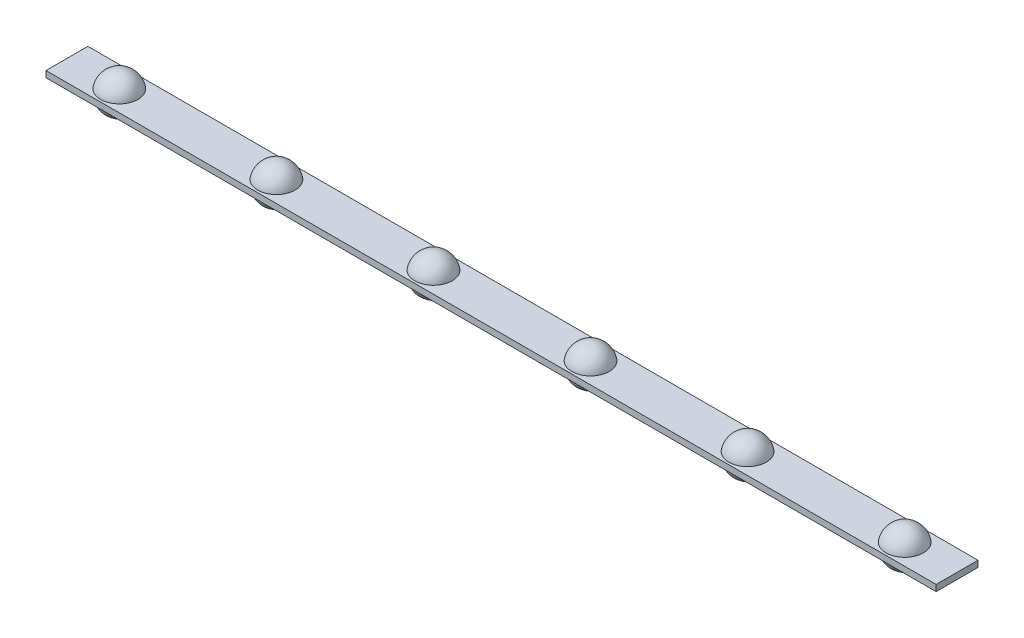
SolidWorks part; units mm, degrees
ref_plane "Front" through (0, 0, 0) normal (0, 0, 1) x (1, 0, 0)
ref_plane "Top" through (0, 0, 0) normal (0, 1, 0) x (1, 0, 0)
ref_plane "Right" through (0, 0, 0) normal (1, 0, 0) x (0, 0, -1)
sketch "Sketch1" plane through (0, 0, 0) normal (1, 0, 0) x (0, 0, -1)
  line L1 (5.6388, 0) -> (-5.6388, 0) construction
  line L4 (-4.1393, 22.8203) -> (-0.7433, 22.6989)
  line L5 (-1.1312, 21.5182) -> (-4.1819, 21.6273)
  line L6 (-4.445, 18.415) -> (-5.6388, 18.415)
  line L7 (-4.445, 21.3734) -> (-4.445, 18.415)
  line L8 (-5.6388, 18.415) -> (-5.6388, 21.3734)
  line L9 (3.9237, 21.6269) -> (0.7619, 21.5441)
  line L10 (5.6388, 0) -> (5.6388, 21.1191)
  line L11 (4.445, 21.1191) -> (4.445, 0)
  line L12 (5.6388, 0) -> (4.445, 0)
  line L13 (-0.7433, 22.6989) -> (3.8925, 22.8203)
  arc A0 (-4.445, 21.3734) -> (-4.1819, 21.6273) centre (-4.191, 21.3734) cw
  arc A1 (-5.6388, 21.3734) -> (-4.1393, 22.8203) centre (-4.191, 21.3734) cw
  arc A3 (3.9237, 21.6269) -> (4.445, 21.1191) centre (3.937, 21.1191) cw
  arc A4 (3.8925, 22.8203) -> (5.6388, 21.1191) centre (3.937, 21.1191) cw
  arc A5 (-1.1312, 21.5182) -> (0.7619, 21.5441) centre (-0.1524, 19.1744) cw
  dimension "D2" = 19.1744
  dimension "D7" = 0.254
  dimension "D8" = 0.508
  dimension "D6" = 2.54
  dimension "D9" = 1.1938
  dimension "D10" = 88.5
  dimension "D1" = 11.2776
  dimension "D3" = 5.7912
  dimension "D4" = 36.83
  dimension "D5" = 1.1938
  dimension "D11" = 87.953
  dimension "D12" = 45.6406
extrude "Extrude1" add sketch "Sketch1" along normal mid plane 400.05
ref_plane "Travel / 2" through (-403.225, 0, 0) normal (-1, 0, 0) x (0, 0, 1)
sketch "Sketch2" plane through (-403.225, 0, 0) normal (-1, 0, 0) x (0, 0, 1)
  line L0 (0.0254, 6.1159) -> (0.0254, 0)
  line L2 (-5.6388, 0) -> (5.6388, 0) construction
  line L3 (5.6388, 21.3734) -> (5.6388, 18.415) construction
  line L7 (-4.445, 21.1191) -> (-4.445, 0) construction
  line L8 (-5.6388, 0) -> (-5.6388, 21.1191) construction
  line L13 (-3.5306, 16.3766) -> (-3.5306, 9.5217)
  line L46 (-2.3867, 7.7262) -> (-0.4146, 6.8065)
  arc A0 (0.0254, 6.1159) -> (-0.4146, 6.8065) centre (-0.7366, 6.1159) ccw
  arc A1 (-1.5056, 17.2916) -> (1.2415, 16.9143) centre (0.1524, 19.1744) ccw
  arc A4 (1.1312, 21.5182) -> (-0.7619, 21.5441) centre (0.1524, 19.1744) ccw construction
  arc A19 (-3.5306, 9.5217) -> (-2.3867, 7.7262) centre (-1.5494, 9.5217) ccw
  arc A25 (-1.5056, 17.2916) -> (-3.5306, 16.3766) centre (-2.3114, 16.3766) ccw
  arc A51 (5.7404, 15.6277) -> (1.2415, 16.9143) centre (2.7686, 13.7451) ccw
  dimension "D2" = 8.4074
  dimension "D3" = 27.4903
  dimension "D6" = 1.9812
  dimension "D8" = 12.2319
  dimension "D10" = 2.5088
  dimension "D11" = 1.2192
  dimension "D4" = 0.762
  dimension "D5" = 4.4704
  dimension "D7" = 115
  dimension "D9" = 19.0435
  dimension "D13" = 11.3792
extrude "Middle Member" add sketch "Sketch2" against normal blind 400.05 separate body thin thin type one direction reverse wall 1.2192
ref_plane "Travel" through (-606.425, 0, 0) normal (-1, 0, 0) x (0, 0, 1)
sketch "Sketch3" plane through (-606.425, 0, 0) normal (-1, 0, 0) x (0, 0, 1)
  line L0 (1.2446, 0) -> (0.0254, 0) construction
  line L1 (-5.6388, 0) -> (-5.6388, 21.1191) construction
  line L56 (7.0612, 0) -> (7.0612, 10.6235)
  line L93 (5.5372, 12.1475) -> (5.1643, 12.1475)
  arc A0 (1.2082, 11.9072) -> (4.2365, 11.8325) centre (2.7686, 13.7451) ccw
  arc A29 (7.0612, 10.6235) -> (5.5372, 12.1475) centre (5.5372, 10.6235) ccw
  arc A53 (5.1643, 12.1475) -> (4.2365, 11.8325) centre (5.1643, 10.6235) ccw
  dimension "D1" = 1.524
  dimension "D4" = 1.524
  dimension "D5" = 2.411
  dimension "D2" = 12.7
  dimension "D3" = 12.1475
  dimension "D6" = 5.853
extrude "Drawer Member" add sketch "Sketch3" against normal blind 400.05 thin thin type one direction wall 1.397
sketch "Sketch6" plane through (0, 0, 7.0612) normal (0, 0, 1) x (1, 0, 0)
  line L1 (-606.425, 0) -> (-604.52, 0)
  line L2 (-606.425, 0) -> (-606.425, 12.1475)
  line L3 (-606.425, 12.1475) -> (-604.52, 12.1475)
  line L4 (-604.52, 0) -> (-604.52, 12.1475)
  line L5 (-206.375, 12.1475) -> (-606.425, 12.1475) construction
  line L7 (-606.425, 10.6235) -> (-606.425, 0) construction
  line L8 (-206.375, 0) -> (-606.425, 0) construction
  dimension "D1" = 1.905
extrude "Cut-Extrude1" cut sketch "Sketch6" against normal through all
sketch "Sketch8" plane through (0, 0, -4.445) normal (0, 0, 1) x (1, 0, 0)
  line L0 (190.3865, 7.6456) -> (191.8208, 7.493)
  line L1 (200.025, 12.2048) -> (190.6284, 12.2048)
  line L2 (191.8208, 7.493) -> (191.8208, 0)
  line L3 (200.025, 0) -> (-200.025, 0) construction
  line L4 (200.025, 21.1191) -> (200.025, 0) construction
  line L5 (200.025, 12.2048) -> (200.025, 0)
  line L6 (200.025, 0) -> (191.8208, 0)
  arc A0 (190.6284, 12.2048) -> (190.3865, 7.6456) centre (190.6284, 9.9188) ccw
  dimension "D3" = 9.9188
  dimension "D1" = 12.2048
  dimension "D2" = 8.2042
  dimension "D4" = 9.3966
  dimension "D5" = 7.493
extrude "Cut-Extrude2" cut sketch "Sketch8" against normal up to next (1.1938 mm away)
sketch "Sketch11" plane through (0, 0, 7.0612) normal (0, 0, 1) x (1, 0, 0)
  line L0 (-212.09, 5.9678) -> (-212.09, 0)
  line L8 (-206.375, 8.5893) -> (-212.2343, 7.2212)
  line L11 (-212.09, 0) -> (-206.375, 0)
  line L12 (-206.375, 0) -> (-206.375, 8.5893)
  arc A1 (-212.2343, 7.2212) -> (-212.09, 5.9678) centre (-212.0899, 6.6028) ccw
  dimension "D3" = 0.635
  dimension "D1" = 5.715
  dimension "D2" = 8.5893
  dimension "D4" = 5.9678
  dimension "D5" = 103.143
extrude "Cut-Extrude3" cut sketch "Sketch11" against normal up to next (1.397 mm away)
sketch "Sketch12" plane through (0, 0, 1.2446) normal (0, 0, 1) x (1, 0, 0)
  line L0 (-3.175, 12.065) -> (-13.335, 12.065)
  line L1 (-3.175, 16.3766) -> (-3.175, 9.5217) construction
  line L2 (-15.875, 9.525) -> (-15.875, 0)
  line L3 (-3.175, 0) -> (-403.225, 0) construction
  line L4 (-15.875, 0) -> (-3.175, 0)
  line L5 (-3.175, 0) -> (-3.175, 12.065)
  arc A0 (-13.335, 12.065) -> (-15.875, 9.525) centre (-13.335, 9.525) ccw
  point P11 (-15.875, 12.065)
  dimension "D3" = 2.54
  dimension "D1" = 12.7
  dimension "D2" = 12.065
extrude "Cut-Extrude4" cut sketch "Sketch12" against normal through all
sketch "Sketch13" plane through (0, 0, -4.445) normal (0, 0, 1) x (1, 0, 0)
  line L0 (-131.6367, 7.112) -> (-156.4652, 7.112)
  line L1 (191.8208, 0) -> (-200.025, 0) construction
  line L2 (-139.7266, 0) -> (-139.7266, 4.2392) construction
  line L3 (-182.5637, 10.287) -> (-131.6367, 10.287)
  line L4 (-200.025, 21.1191) -> (-200.025, 0) construction
  line L5 (-160.2752, 7.112) -> (-182.5637, 7.112)
  line L6 (-159.5132, 0) -> (-159.5132, 6.35)
  line L7 (-157.2272, 6.35) -> (-157.2272, 0)
  line L8 (-137.2501, 2.286) -> (-142.2031, 2.286)
  line L13 (-176.3026, 0) -> (-171.7306, 0)
  line L14 (-168.2, 0) -> (-161.85, 0)
  line L15 (-159.5132, 0) -> (-157.2272, 0)
  line L16 (-154.7126, 0) -> (-150.1406, 0)
  line L17 (-144.4891, 0) -> (-134.9641, 0)
  arc A1 (-182.5637, 10.287) -> (-182.5637, 7.112) centre (-182.5637, 8.6995) ccw
  arc A2 (-159.5132, 6.35) -> (-160.2752, 7.112) centre (-160.2752, 6.35) ccw
  arc A4 (-156.4652, 7.112) -> (-157.2272, 6.35) centre (-156.4652, 6.35) ccw
  arc A7 (-131.6367, 7.112) -> (-131.6367, 10.287) centre (-131.6367, 8.6995) ccw
  arc A8 (-161.85, 0) -> (-168.2, 0) centre (-165.025, 0) ccw
  arc A9 (-171.7306, 0) -> (-176.3026, 0) centre (-174.0166, 0) ccw
  arc A10 (-150.1406, 0) -> (-154.7126, 0) centre (-152.4266, 0) ccw
  arc A11 (-134.9641, 0) -> (-137.2501, 2.286) centre (-137.2501, 0) ccw
  arc A12 (-142.2031, 2.286) -> (-144.4891, 0) centre (-142.2031, 0) ccw
  dimension "D3" = 2.286
  dimension "D4" = 3.175
  dimension "D7" = 8.9916
  dimension "D8" = 21.59
  dimension "D9" = 34.29
  dimension "D10" = 0.762
  dimension "D11" = 17.5387
  dimension "D12" = 9.525
  dimension "D13" = 5.5118
  dimension "D14" = 35
  dimension "D1" = 3.175
  dimension "D2" = 50.927
  dimension "D5" = 2.286
  dimension "D6" = 10.287
extrude "Cut-Extrude5" cut sketch "Sketch13" against normal up to next (1.1938 mm away)
sketch "Sketch32" plane through (0, 0, -5.6388) normal (0, 0, -1) x (-1, 0, 0)
  line L0 (19.5625, 0) -> (29.0875, 0)
  line L1 (33.85, 0) -> (40.2, 0)
  line L2 (43.6925, 0) -> (53.2175, 0)
  line L3 (56.583, 0) -> (61.155, 0)
  line L4 (-191.8208, 0) -> (134.9641, 0) construction
  line L5 (182.5637, 10.287) -> (131.6367, 10.287) construction
  line L6 (131.6367, 7.112) -> (156.4652, 7.112) construction
  line L7 (48.455, 2.286) -> (48.455, -3.4269) construction
  line L8 (24.325, 2.286) -> (24.325, -3.4269) construction
  line L14 (16.3875, 10.287) -> (59.631, 10.287)
  line L15 (55.059, 7.112) -> (16.3875, 7.112)
  line L17 (61.155, 8.763) -> (61.155, 0)
  line L18 (56.583, 0) -> (56.583, 5.588)
  line L23 (21.8485, 2.286) -> (26.8015, 2.286)
  line L25 (45.9785, 2.286) -> (50.9315, 2.286)
  arc A0 (168.2, 0) -> (161.85, 0) centre (165.025, 0) ccw construction
  arc A13 (61.155, 8.763) -> (59.631, 10.287) centre (59.631, 8.763) ccw
  arc A14 (56.583, 5.588) -> (55.059, 7.112) centre (55.059, 5.588) ccw
  arc A17 (16.3875, 10.287) -> (16.3875, 7.112) centre (16.3875, 8.6995) ccw
  arc A20 (29.0875, 0) -> (26.8015, 2.286) centre (26.8015, 0) ccw
  arc A21 (21.8485, 2.286) -> (19.5625, 0) centre (21.8485, 0) ccw
  arc A22 (40.2, 0) -> (33.85, 0) centre (37.025, 0) ccw
  arc A24 (53.2175, 0) -> (50.9315, 2.286) centre (50.9315, 0) ccw
  arc A25 (45.9785, 2.286) -> (43.6925, 0) centre (45.9785, 0) ccw
  dimension "D2" = 1.524
  dimension "D3" = 3.175
  dimension "D4" = 9.525
  dimension "D5" = 2.286
  dimension "D6" = 11.43
  dimension "D7" = 12.7
  dimension "D8" = 24.13
  dimension "D9" = 20.6375
  dimension "D10" = 128
  dimension "D1" = 4.572
extrude "Cut-Extrude14" cut sketch "Sketch32" against normal up to next (1.1938 mm away)
sketch "Sketch33" plane through (83.6094, 0.8125, -5.6388) normal (0, 0, -1) x (-1, 0, 0)
  line L0 (7.1719, -0.8125) -> (16.6969, -0.8125) construction
  line L1 (21.4594, -0.8125) -> (27.8094, -0.8125)
  line L2 (31.3019, -0.8125) -> (40.8269, -0.8125)
  line L3 (44.1924, -0.8125) -> (48.7644, -0.8125)
  line L4 (9.6484, -0.8125) -> (14.2204, -0.8125)
  line L7 (36.0644, 1.4735) -> (36.0644, -4.2394) construction
  line L8 (11.9344, 1.4735) -> (11.9344, -3.4269) construction
  line L9 (-108.2114, -0.8125) -> (103.1719, -0.8125) construction
  line L10 (143.2404, 9.4745) -> (99.9969, 9.4745) construction
  line L11 (99.9969, 6.2995) -> (138.6684, 6.2995) construction
  line L14 (3.9969, 9.4745) -> (47.2404, 9.4745)
  line L15 (42.6684, 6.2995) -> (3.9969, 6.2995)
  line L17 (48.7644, 7.9505) -> (48.7644, -0.8125)
  line L18 (44.1924, -0.8125) -> (44.1924, 4.7755)
  line L23 (9.4579, 1.4735) -> (14.4109, 1.4735) construction
  line L25 (33.5879, 1.4735) -> (38.5409, 1.4735)
  arc A0 (14.2204, -0.8125) -> (9.6484, -0.8125) centre (11.9344, -0.8125) ccw
  arc A1 (251.8094, -0.8125) -> (245.4594, -0.8125) centre (248.6344, -0.8125) ccw construction
  arc A13 (48.7644, 7.9505) -> (47.2404, 9.4745) centre (47.2404, 7.9505) ccw
  arc A14 (44.1924, 4.7755) -> (42.6684, 6.2995) centre (42.6684, 4.7755) ccw
  arc A17 (3.9969, 9.4745) -> (3.9969, 6.2995) centre (3.9969, 7.887) ccw
  arc A20 (16.6969, -0.8125) -> (14.4109, 1.4735) centre (14.4109, -0.8125) ccw construction
  arc A21 (9.4579, 1.4735) -> (7.1719, -0.8125) centre (9.4579, -0.8125) ccw construction
  arc A22 (27.8094, -0.8125) -> (21.4594, -0.8125) centre (24.6344, -0.8125) ccw
  arc A24 (40.8269, -0.8125) -> (38.5409, 1.4735) centre (38.5409, -0.8125) ccw
  arc A25 (33.5879, 1.4735) -> (31.3019, -0.8125) centre (33.5879, -0.8125) ccw
  dimension "D2" = 1.524
  dimension "D3" = 3.175
  dimension "D4" = 9.525
  dimension "D5" = 2.286
  dimension "D6" = 11.43
  dimension "D7" = 12.7
  dimension "D8" = 24.13
  dimension "D9" = 20.6375
  dimension "D10" = 224
  dimension "D1" = 4.572
extrude "Cut F" cut sketch "Sketch33" against normal up to next (1.1938 mm away)
sketch "Sketch34" plane through (169.8236, 1.4527, -5.6388) normal (0, 0, -1) x (-1, 0, 0)
  line L0 (-2.6539, -1.4527) -> (6.8711, -1.4527)
  line L1 (11.6336, -1.4527) -> (17.9836, -1.4527)
  line L2 (21.4761, -1.4527) -> (31.0011, -1.4527)
  line L3 (34.3666, -1.4527) -> (38.9386, -1.4527)
  line L4 (-21.9972, -1.4527) -> (95.8626, -1.4527) construction
  line L7 (26.2386, 0.8333) -> (26.2386, -4.8796) construction
  line L8 (2.1086, 0.8333) -> (2.1086, -4.0671) construction
  line L9 (229.4546, 8.8343) -> (186.2111, 8.8343) construction
  line L10 (186.2111, 5.6593) -> (224.8826, 5.6593) construction
  line L14 (-5.8289, 8.8343) -> (37.4146, 8.8343)
  line L15 (32.8426, 5.6593) -> (-5.8289, 5.6593)
  line L17 (38.9386, 7.3103) -> (38.9386, -1.4527)
  line L18 (34.3666, -1.4527) -> (34.3666, 4.1353)
  line L23 (-0.3679, 0.8333) -> (4.5851, 0.8333)
  line L25 (23.7621, 0.8333) -> (28.7151, 0.8333)
  arc A0 (338.0236, -1.4527) -> (331.6736, -1.4527) centre (334.8486, -1.4527) ccw construction
  arc A13 (38.9386, 7.3103) -> (37.4146, 8.8343) centre (37.4146, 7.3103) ccw
  arc A14 (34.3666, 4.1353) -> (32.8426, 5.6593) centre (32.8426, 4.1353) ccw
  arc A17 (-5.8289, 8.8343) -> (-5.8289, 5.6593) centre (-5.8289, 7.2468) ccw
  arc A20 (6.8711, -1.4527) -> (4.5851, 0.8333) centre (4.5851, -1.4527) ccw
  arc A21 (-0.3679, 0.8333) -> (-2.6539, -1.4527) centre (-0.3679, -1.4527) ccw
  arc A22 (17.9836, -1.4527) -> (11.6336, -1.4527) centre (14.8086, -1.4527) ccw
  arc A24 (31.0011, -1.4527) -> (28.7151, 0.8333) centre (28.7151, -1.4527) ccw
  arc A25 (23.7621, 0.8333) -> (21.4761, -1.4527) centre (23.7621, -1.4527) ccw
  dimension "D2" = 1.524
  dimension "D3" = 3.175
  dimension "D4" = 9.525
  dimension "D5" = 2.286
  dimension "D6" = 11.43
  dimension "D7" = 12.7
  dimension "D8" = 24.13
  dimension "D9" = 20.6375
  dimension "D10" = 320.04
  dimension "D1" = 4.572
extrude "Cut G" cut sketch "Sketch34" against normal up to next (1.1938 mm away)
sketch "Sketch31" plane through (0, 0, -5.6388) normal (0, 0, -1) x (-1, 0, 0)
  line L0 (-200.025, 12.2048) -> (-200.025, 21.1191) construction
  line L1 (-191.8208, 0) -> (-172.4775, 0) construction
  line L2 (-184.15, 0) -> (-177.8, 0)
  arc A0 (-177.8, 0) -> (-184.15, 0) centre (-180.975, 0) ccw
  dimension "D1" = 19.05
  dimension "D2" = 6.35
extrude "Cut-Extrude15" cut sketch "Sketch31" against normal up to next (1.1938 mm away)
sketch "Sketch26" plane through (0, 0, 1.2446) normal (0, 0, 1) x (1, 0, 0)
  line L0 (-176.3026, 0) -> (-134.9641, 0)
  line L1 (-171.4766, 4.826) -> (-139.7901, 4.826)
  line L2 (-19.5625, 0) -> (-53.2175, 0)
  line L3 (-48.3915, 4.826) -> (-24.3885, 4.826)
  line L4 (76.4375, 0) -> (42.7825, 0)
  line L5 (47.6085, 4.826) -> (71.6115, 4.826)
  arc A0 (-176.3026, 0) -> (-171.4766, 4.826) centre (-171.4766, 0) cw
  arc A1 (-134.9641, 0) -> (-139.7901, 4.826) centre (-139.7901, 0) ccw
  arc A2 (-53.2175, 0) -> (-48.3915, 4.826) centre (-48.3915, 0) cw
  arc A3 (-24.3885, 4.826) -> (-19.5625, 0) centre (-24.3885, 0) cw
  arc A4 (-19.5625, 0) -> (-21.8485, 2.286) centre (-21.8485, 0) ccw construction
  arc A5 (-50.9315, 2.286) -> (-53.2175, 0) centre (-50.9315, 0) ccw construction
  arc A6 (42.7825, 0) -> (47.6085, 4.826) centre (47.6085, 0) cw
  arc A7 (71.6115, 4.826) -> (76.4375, 0) centre (71.6115, 0) cw
  dimension "D1" = 4.826
extrude "Cut-Extrude17" cut sketch "Sketch26" against normal up to next (1.2192 mm away)
ref_plane "Plane3" through (-187.325, 0, 0) normal (-1, 0, 0) x (0, 0, 1)
sketch "Sketch27" plane through (-187.325, 0, 0) normal (-1, 0, 0) x (0, 0, 1)
  line L0 (0.1524, 21.6832) -> (0.1524, 16.6656)
  line L1 (0.1524, 23.635) -> (0.1524, 15.2838) construction
  arc A0 (0.1524, 16.6656) -> (0.1524, 21.6832) centre (0.1524, 19.1744) ccw
  arc A1 (-1.5056, 17.2916) -> (1.2415, 16.9143) centre (0.1524, 19.1744) ccw construction
revolve "Revolve1" add sketch "Sketch27" angle 360 about L1
pattern_linear "LPattern1" count 6 spacing 19.05 along (1, 0, 0) of bodies 128
sketch "Sketch28" plane through (-187.325, 0, 0) normal (-1, 0, 0) x (0, 0, 1)
  line L0 (2.6612, 19.1744) -> (-2.3564, 19.1744) construction
  line L1 (3.9624, 18.7934) -> (-3.6576, 18.7934)
  line L2 (3.9624, 18.7934) -> (3.9624, 19.5554)
  line L3 (3.9624, 19.5554) -> (-3.6576, 19.5554)
  line L4 (-3.6576, 18.7934) -> (-3.6576, 19.5554)
  line L5 (0.1524, 20.5465) -> (0.1524, 17.804) construction
  circle A1 centre (0.1524, 19.1744) radius 2.5088 construction
  point P8 (0.1524, 19.1744)
  dimension "D1" = 7.62
  dimension "D2" = 0.762
extrude "Extrude7" add sketch "Sketch28" along normal blind 6.35 and the other way blind 101.6
ref_plane "Plane4" through (-365.125, 0, 0) normal (-1, 0, 0) x (0, 0, 1)
sketch "Sketch29" plane through (-365.125, 0, 0) normal (-1, 0, 0) x (0, 0, 1)
  line L0 (2.7686, 16.0438) -> (2.7686, 11.4464)
  line L1 (2.7686, 16.6801) -> (2.7686, 10.2973) construction
  arc A0 (2.7686, 11.4464) -> (2.7686, 16.0438) centre (2.7686, 13.7451) ccw
  arc A1 (4.7105, 14.9753) -> (1.7707, 15.816) centre (2.7686, 13.7451) ccw construction
revolve "Revolve2" add sketch "Sketch29" angle 360 about L1
pattern_linear "LPattern2" count 6 spacing 19.05 along (1, 0, 0) of bodies 135
sketch "Sketch30" plane through (-365.125, 0, 0) normal (-1, 0, 0) x (0, 0, 1)
  line L0 (0.4699, 13.7451) -> (5.0673, 13.7451) construction
  line L1 (3.9624, 18.7934) -> (3.9624, 19.5554) construction
  line L2 (0.2286, 14.1261) -> (5.3086, 14.1261)
  line L3 (0.2286, 14.1261) -> (0.2286, 13.3641)
  line L4 (0.2286, 13.3641) -> (5.3086, 13.3641)
  line L5 (5.3086, 14.1261) -> (5.3086, 13.3641)
  line L7 (2.7686, 14.2437) -> (2.7686, 12.7853) construction
  circle A0 centre (2.7686, 13.7451) radius 2.2987 construction
  point P4 (2.7686, 13.7451)
  dimension "D1" = 5.08
extrude "Extrude8" add sketch "Sketch30" along normal blind 6.35 and the other way blind 101.6
mirror "Mirror3" about plane through (0, 0, 0) normal (0, 1, 0) of bodies 118 163 159 117 124 126 127 119
mirror "Mirror5" about plane through (0, 0, 0) normal (0, 1, 0) of bodies 141 134
delete or keep bodies "Sólido-Eliminar/Conservar 1" type delete bodies bodies 150
delete or keep bodies "Sólido-Eliminar/Conservar 2" type delete bodies bodies 162
delete or keep bodies "Sólido-Eliminar/Conservar 3" type delete bodies bodies 161
delete or keep bodies "Sólido-Eliminar/Conservar 4" type delete bodies bodies 134
delete or keep bodies "Sólido-Eliminar/Conservar 5" type delete bodies bodies 153
delete or keep bodies "Sólido-Eliminar/Conservar 6" type delete bodies bodies 152
